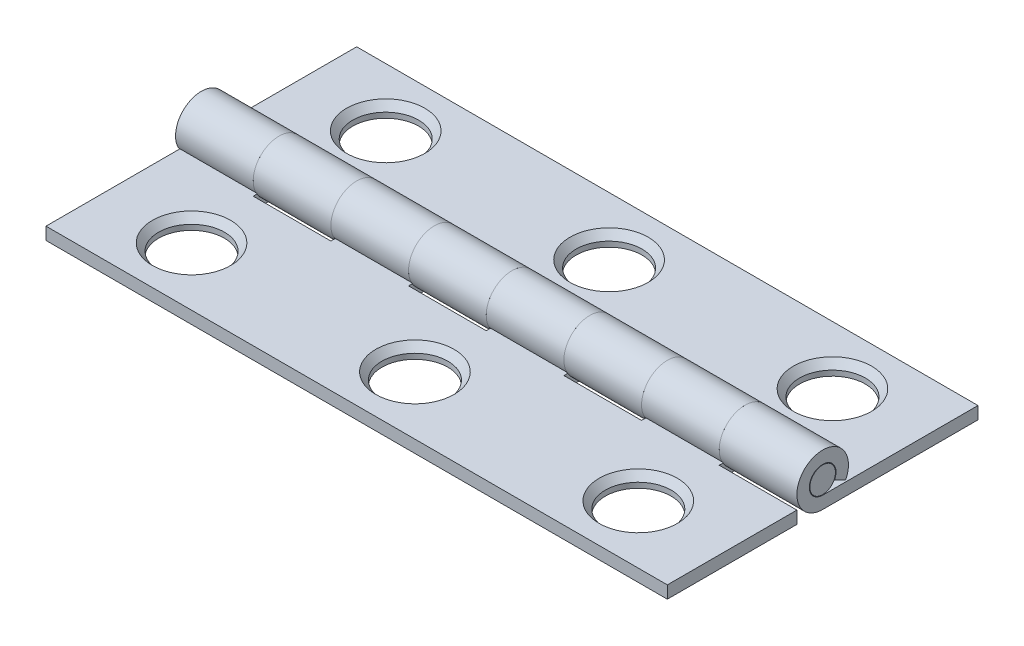
SolidWorks part; units mm, degrees
ref_plane "Front Plane" through (0, 0, 0) normal (0, 0, 1) x (1, 0, 0)
ref_plane "Top Plane" through (0, 0, 0) normal (0, 1, 0) x (1, 0, 0)
ref_plane "Right Plane" through (0, 0, 0) normal (1, 0, 0) x (0, 0, -1)
sketch "Sketch1" plane through (0, 0, 0) normal (0, 1, 0) x (1, 0, 0)
  line L0 (-25.4, 0) -> (25.4, 0) construction
  line L1 (-25.4, -12.7) -> (-25.4, 12.7) construction
  line L2 (-25.4, -12.7) -> (-18.2626, -12.7) construction
  line L3 (-18.2626, -12.7) -> (0, -12.7) construction
  line L4 (0, -12.7) -> (18.2626, -12.7) construction
  line L5 (25.4, -12.7) -> (25.4, -7.9375) construction
  line L6 (18.2626, -12.7) -> (25.4, -12.7) construction
  line L7 (-25.4, 12.7) -> (-18.2626, 12.7) construction
  line L8 (-18.2626, 12.7) -> (0, 12.7) construction
  line L9 (0, 12.7) -> (18.2626, 12.7) construction
  line L10 (18.2626, 12.7) -> (25.4, 12.7) construction
  line L11 (18.2626, -11.1379) -> (18.2626, -4.7371) construction
  line L12 (18.2626, -7.9375) -> (25.4, -7.9375) construction
  point P3 (18.2626, -10.6299)
  point P4 (0, 0)
  point P8 (-25.4, 0)
  point P17 (-19.05, 0)
  point P21 (18.2626, -7.9375)
  dimension "Frame Leaf Height" = 50.8
  dimension "Overall Width" = 25.4
  dimension "Hole to End 1" = 7.1374
  dimension "Hole Spacing" = 18.2626
  dimension "D3" = 18.2626
  dimension "Hole to End 2" = 7.1374
  dimension "D1" = 7.1374
  dimension "D2" = 7.1374
  dimension "D4" = 18.2626
  dimension "D6" = 18.2626
  dimension "Knuckle Length" = 6.35
  dimension "Hole Chamfer Dia" = 6.4008
  dimension "Hole Center to Pin" = 7.9375
  dimension "Door Leaf Height" = 50.8
  dimension "Frame Leaf Width" = 12.7
  dimension "Door Leaf Width" = 12.7
  dimension "Mounting Hole Diameter" = 5.3848
sketch "Sketch2" plane through (0, 0, 0) normal (1, 0, 0) x (0, 0, -1)
  line L2 (0, -2.1082) -> (0, -1.0922) construction
  line L4 (0, 1.0922) -> (0, -1.0922) construction
  point P8 (0, 0)
  dimension "Leaf Thickness" = 1.016
  dimension "Pin Diameter" = 2.1844
sketch "Sketch3" plane through (0, 0, 0) normal (1, 0, 0) x (0, 0, -1)
  line L3 (0, 0) -> (-2.1082, -1.0922) construction
  line L4 (0, -2.1082) -> (-12.7, -2.1082)
  line L5 (-12.7, -2.1082) -> (-12.7, -1.0922)
  line L7 (-12.7, -1.0922) -> (0, -1.0922)
  line L8 (-12.7, 0) -> (12.7, 0) construction
  line L9 (-0.9698, -0.5024) -> (-1.8719, -0.9698)
  line L11 (-2.1082, 0) -> (-2.1082, -1.0922) construction
  circle A4 centre (0, 0) radius 1.0922 construction
  circle A5 centre (0, 0) radius 2.1082 construction
  arc A8 (-0.9698, -0.5024) -> (0, -1.0922) centre (0, 0) cw
  arc A9 (-1.8719, -0.9698) -> (0, -2.1082) centre (0, 0) cw
  point P0 (-1.8719, -0.9698)
  point P13 (-0.9698, -0.5024)
extrude "Boss-Extrude1" add sketch "Sketch3" along normal mid plane 50.8
sketch "Sketch4" plane through (0, 0, 0) normal (0, 1, 0) x (1, 0, 0)
  line L0 (-25.4, -2.1082) -> (25.4, -2.1082) construction
  line L1 (-25.4, -2.1082) -> (25.4, -2.1082) construction
  line L2 (25.4, 2.1082) -> (-25.4, 2.1082) construction
  line L3 (25.4, 2.1082) -> (-25.4, 2.1082) construction
  line L4 (-19.05, -2.1082) -> (-19.05, 2.1082)
  line L6 (-19.05, 2.1082) -> (-12.7, 2.1082)
  line L7 (-12.7, -2.1082) -> (-19.05, -2.1082)
  line L8 (-12.7, 2.1082) -> (-12.7, -2.1082)
  point P8 (-19.05, 0)
  dimension "D1" = 6.35
extrude "Cut-Extrude1" cut sketch "Sketch4" against normal through all both and the other way through all
pattern_linear "LPattern1" count 6 spacing 12.7 along (1, 0, 0) of "Cut-Extrude1"
sketch "Sketch5" plane through (0, -1.0922, 0) normal (0, 1, 0) x (1, 0, 0)
  line L0 (18.2626, -7.9375) -> (-18.2626, -7.9375) construction
  line L1 (0, -7.9375) -> (0, -12.7) construction
  line L2 (-18.2626, -7.9375) -> (-18.2626, -12.7) construction
  circle A0 centre (18.2626, -7.9375) radius 3.2004
  circle A1 centre (0, -7.9375) radius 3.2004
  circle A2 centre (-18.2626, -7.9375) radius 3.2004
extrude "Cut-Extrude2" cut sketch "Sketch5" against normal through all draft 41
sketch "Sketch9" plane through (0, 0, 0) normal (0, 1, 0) x (1, 0, 0)
  circle A0 centre (18.2626, -7.9375) radius 2.6924
  circle A1 centre (0, -7.9375) radius 2.6924
  circle A2 centre (-18.2626, -7.9375) radius 2.6924
  dimension "D1" = 5.3848
extrude "Cut-Extrude3" cut sketch "Sketch9" against normal through all both and the other way through all
pattern_circular "CirPattern1" count 2 over 360 about axis through (0, 1.0922, 0) along (0, -1, 0) reverse direction yes of bodies 110 107
sketch "Sketch6" plane through (0, 0, 0) normal (1, 0, 0) x (0, 0, -1)
  circle A0 centre (0, 0) radius 1.0922
  dimension "D1" = 2.1844
extrude "Boss-Extrude2" add sketch "Sketch6" along normal mid plane 50.8 separate body
chamfer "Chamfer1" distance 0.0437 angle 45 2 edges at (25.4, 0, -1.0922) (-25.4, 0, -1.0922)
sketch "Sketch7" plane through (0, 0, 0) normal (1, 0, 0) x (0, 0, -1)
  line L0 (-1.0922, 0) -> (1.0922, 0) construction
  line L1 (-12.7, 0) -> (12.7, 0) construction
  line L2 (12.7, -1.0922) -> (12.7, -2.1082) construction
  line L3 (12.7, -1.0922) -> (12.7, -2.1082) construction
  line L4 (12.7, -2.1082) -> (-12.7, -2.1082) construction
  line L5 (-12.7, -2.1082) -> (-12.7, -1.0922)
  point P6 (0, 0)
  point P8 (1.0922, 0)
  point P9 (-1.0922, 0)
  point P12 (12.7, -1.0922)
  point P13 (12.7, -2.1082)
  point P14 (-12.7, -2.1082)
  dimension "D1" = 2.1844
  dimension "D2" = 25.4
  dimension "D3" = 1.016
sketch "Sketch8" plane through (0, 0, 0) normal (0, 1, 0) x (1, 0, 0)
  line L0 (-21.463, -7.9375) -> (-15.0622, -7.9375) construction
  line L1 (-3.2004, -7.9375) -> (3.2004, -7.9375) construction
  line L2 (15.0622, -7.9375) -> (21.463, -7.9375) construction
  line L3 (-18.2626, -4.7371) -> (-18.2626, -11.1379) construction
  line L4 (0, -4.7371) -> (0, -11.1379) construction
  line L5 (18.2626, -4.7371) -> (18.2626, -11.1379) construction
  line L6 (-18.2626, 11.1379) -> (-18.2626, 4.7371) construction
  line L7 (-21.463, 7.9375) -> (-15.0622, 7.9375) construction
  line L8 (0, 11.1379) -> (0, 4.7371) construction
  line L9 (-3.2004, 7.9375) -> (3.2004, 7.9375) construction
  line L10 (18.2626, 11.1379) -> (18.2626, 4.7371) construction
  line L11 (15.0622, 7.9375) -> (21.463, 7.9375) construction
  line L12 (18.2626, 7.9375) -> (20.5256, 10.2005) construction
  circle A1 centre (-18.2626, -7.9375) radius 3.2004 construction
  circle A2 centre (0, -7.9375) radius 3.2004 construction
  circle A3 centre (18.2626, -7.9375) radius 3.2004 construction
  circle A4 centre (-18.2626, 7.9375) radius 3.2004 construction
  circle A5 centre (0, 7.9375) radius 3.2004 construction
  circle A6 centre (18.2626, 7.9375) radius 3.2004 construction
  circle A7 centre (18.2626, 7.9375) radius 3.2004 construction
  point P2 (-25.4, 0)
  point P7 (-18.2626, -7.9375)
  point P13 (0, -7.9375)
  point P19 (18.2626, -7.9375)
  point P25 (-25.4, 12.7)
  point P26 (25.4, 12.7)
  point P28 (-25.4, -12.7)
  point P30 (25.4, -12.7)
  point P32 (-21.463, -7.9375)
  point P33 (-18.2626, -4.7371)
  point P34 (-15.0622, -7.9375)
  point P35 (-18.2626, -11.1379)
  point P36 (0, -11.1379)
  point P37 (-3.2004, -7.9375)
  point P38 (0, -4.7371)
  point P39 (3.2004, -7.9375)
  point P40 (21.463, -7.9375)
  point P41 (18.2626, -11.1379)
  point P42 (15.0622, -7.9375)
  point P43 (18.2626, -4.7371)
  point P66 (0, -12.7)
  point P67 (18.2626, -12.7)
  point P69 (-18.2626, -12.7)
  point P71 (-18.2626, 12.7)
  point P73 (-18.2626, 7.9375)
  point P75 (0, 7.9375)
  point P76 (18.2626, 7.9375)
  point P77 (18.2626, 12.7)
  point P78 (0, 12.7)
  point P82 (-18.2626, 11.1379)
  point P83 (-21.463, 7.9375)
  point P84 (-18.2626, 4.7371)
  point P85 (-15.0622, 7.9375)
  point P86 (0, 4.7371)
  point P87 (-3.2004, 7.9375)
  point P88 (0, 11.1379)
  point P89 (3.2004, 7.9375)
  point P90 (18.2626, 4.7371)
  point P91 (15.0622, 7.9375)
  point P92 (18.2626, 11.1379)
  point P93 (21.463, 7.9375)
  point P97 (20.5256, 10.2005)
  dimension "D1" = 45
equation "\"D3@Sketch1\"=\"Hole Spacing@Sketch1\""
equation "\"D1@Sketch1\"=\"Hole to End 1@Sketch1\""
equation "\"D2@Sketch1\"=\"Hole to End 2@Sketch1\""
equation "\"D4@Sketch1\"=\"Hole Spacing@Sketch1\""
equation "\"D6@Sketch1\"=\"D4@Sketch1\""
equation "\"D1@Boss-Extrude1\" = \"Frame Leaf Height@Sketch1\""
equation "\"D1@Sketch4\"=\"Knuckle Length@Sketch1\""
equation "\"D3@LPattern1\"=\"Knuckle Length@Sketch1\"*2"
equation "\"D1@Sketch6\"=\"Pin Diameter@Sketch2\""
equation "\"D1@Boss-Extrude2\" = \"Frame Leaf Height@Sketch1\""
equation "\"D1@Sketch7\"=\"Pin Diameter@Sketch2\""
equation "\"D2@Sketch7\"=\"Overall Width@Sketch1\""
equation "\"D3@Sketch7\"=\"Leaf Thickness@Sketch2\""
equation "\"Knuckle Length@Sketch1\" = \"Frame Leaf Height@Sketch1\" / 8"
equation "\"Hole to End 2@Sketch1\"=\"Hole to End 1@Sketch1\""
equation "\"D1@Sketch9\"=\"Mounting Hole Diameter@Sketch1\""
equation "\"D1@Chamfer1\"=\"Pin Diameter@Sketch2\"*.02"
